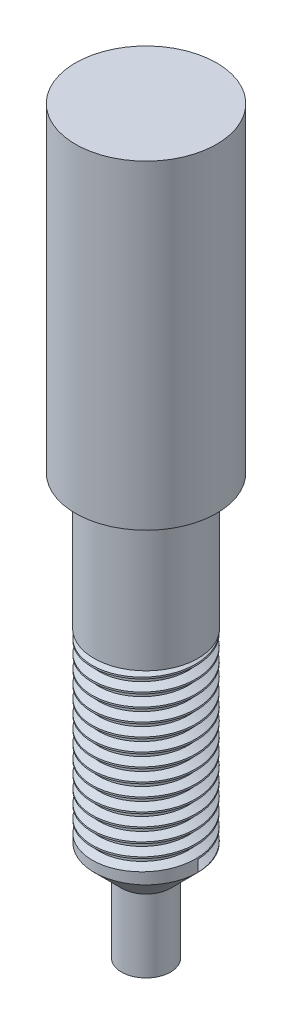
SolidWorks part; units mm, degrees
ref_plane "Front Plane" through (0, 0, 0) normal (0, 0, 1) x (1, 0, 0)
ref_plane "Top Plane" through (0, 0, 0) normal (0, 1, 0) x (1, 0, 0)
ref_plane "Right Plane" through (0, 0, 0) normal (1, 0, 0) x (0, 0, -1)
sketch "Sketch2" plane through (0, 0, 0) normal (0, 0, 1) x (1, 0, 0)
  line L0 (0, 0) -> (0, 508.8276) construction
  line L1 (0, 0) -> (6, 0)
  line L2 (0, 0) -> (0, 25.4)
  line L3 (0, 25.4) -> (6, 25.4)
  line L4 (6, 0) -> (6, 25.4)
  line L5 (0, 25.4) -> (12.6746, 25.4)
  line L6 (0, 25.4) -> (0, 69.85)
  line L7 (0, 69.85) -> (12.6746, 69.85)
  line L8 (12.6746, 25.4) -> (12.6746, 69.85)
  line L9 (0, 69.85) -> (12.721, 69.85)
  line L10 (0, 69.85) -> (0, 102.87)
  line L11 (0, 102.87) -> (12.721, 102.87)
  line L12 (12.721, 69.85) -> (12.721, 102.87)
  line L13 (0, 102.87) -> (17.272, 102.87)
  line L14 (0, 102.87) -> (0, 181.102)
  line L15 (0, 181.102) -> (17.272, 181.102)
  line L16 (17.272, 102.87) -> (17.272, 181.102)
  dimension "D1" = 78.232
  dimension "D2" = 17.272
  dimension "D4" = 33.02
  dimension "D3" = 12.721
  dimension "D5" = 44.45
  dimension "D6" = 12.6746
  dimension "D7" = 25.4
  dimension "D8" = 6
revolve "Revolve1" add sketch "Sketch2" angle 360 about L0 region at (3, 12.7, 0) region at (6.3373, 47.625, 0) region at (6.3605, 86.36, 0) region at (8.636, 141.986, 0)
chamfer "Chamfer1" distance 7.62 angle 45 1 edges at (0, 25.4, -6)
thread "Thread1" pitch 3.175 method cut profile "Thread Profile1" start angle 0, offset 0, length 0, pitch 3.175, diameter 25.3492
ref_plane "Plane1" through (12.6746, 24.4546, 0) normal (0, 0, 1) x (1, 0, 0)
sketch "Thread Profile1" plane through (12.6746, 24.4546, 0) normal (0, 0, 1) x (1, 0, 0)
  line L0 (0, 0) -> (0, 3.175) construction
  line L11 (0, 0) -> (0, 2.7781)
  line L12 (0, 2.7781) -> (-1.7185, 1.7859)
  line L13 (-1.7185, 1.7859) -> (-1.7185, 0.9922)
  line L15 (-1.7185, 0.9922) -> (0, 0)
  line L17 (-1.7185, 1.3891) -> (0, 1.3891) construction
  point P2 (0, 0)
  dimension "Pitch" = 3.175
  dimension "Profile_Angle" = 60
  dimension "Profile_Land" = 0.7937
  dimension "Profile_Height" = 1.7185
equation "\"hole diamiter\"= 1.36in"
equation "\"wheel depth\"= 2.88"
equation "\"press_tolerance\"= 0.00165"
equation "\"wheel_connection\" = \"hole diamiter\"'https://at-machining.com/tolerance-press-fit/"
equation "\"D1@Sketch2\"=\"wheel depth\"+0.2"
equation "\"D2@Sketch2\"=\"wheel_connection\"/2"
equation "\"fitting depth\" = 1.3"
equation "\"D4@Sketch2\"=\"fitting depth\""
equation "\"bearing_id\"= 1"
equation "\"bearing_connection\"= \"bearing_id\" + \"press_tolerance\"'https://at-machining.com/tolerance-press-fit/"
equation "\"D3@Sketch2\"=\"bearing_connection\"/2"
equation "\"thread length\"= 1.75"
equation "\"major_diamiter\" = 0.9980'https://www.machiningdoctor.com/threadinfo/?tid=109"
equation "\"D5@Sketch2\"=\"thread length\""
equation "\"D6@Sketch2\"=\"major_diamiter\"/2"
equation "\"coupling diamiter\"= 12mm"
equation "\"coupling lenght\"=1"
equation "\"D7@Sketch2\"=\"coupling lenght\""
equation "\"D8@Sketch2\"=\"coupling diamiter\"/2"
